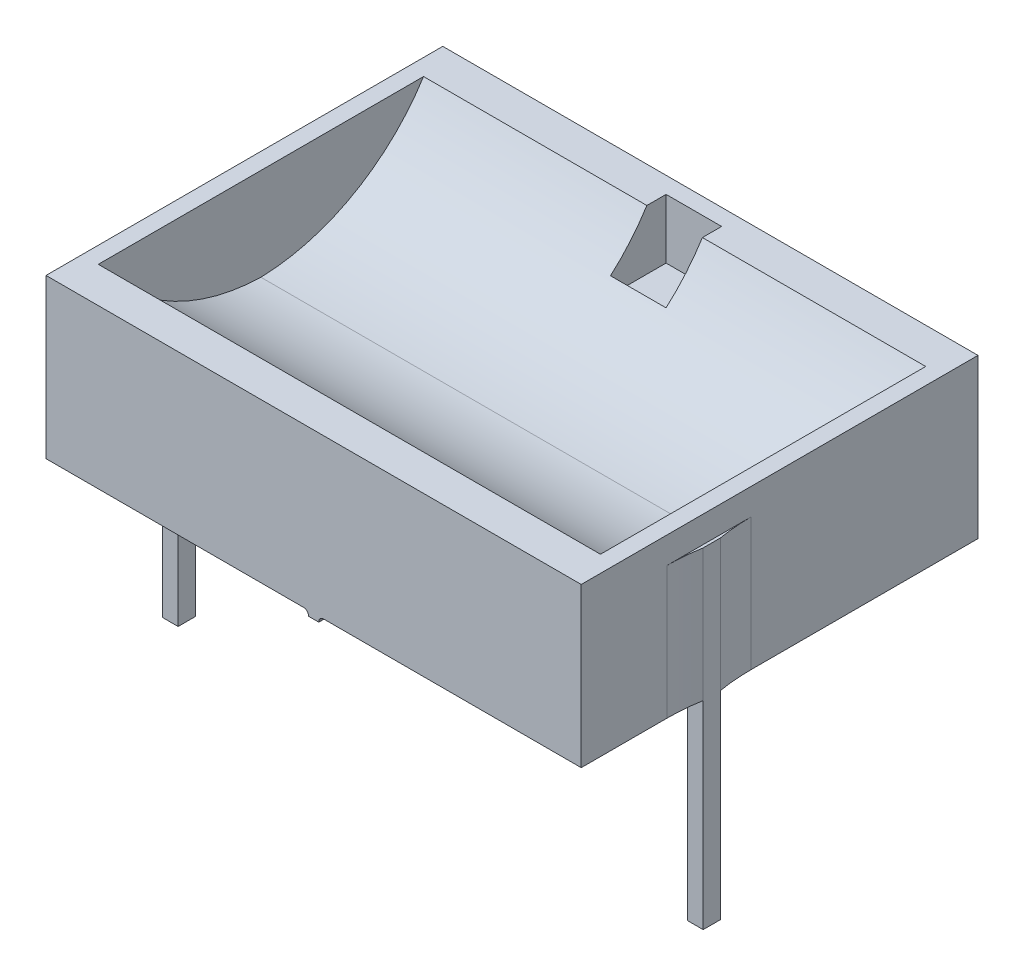
SolidWorks part; units mm, degrees
ref_plane "Front Plane" through (0, 0, 0) normal (0, 0, 1) x (1, 0, 0)
ref_plane "Top Plane" through (0, 0, 0) normal (0, 1, 0) x (1, 0, 0)
ref_plane "Right Plane" through (0, 0, 0) normal (1, 0, 0) x (0, 0, -1)
sketch "Sketch1" plane through (0, 0, 0) normal (0, 1, 0) x (1, 0, 0)
  line L1 (0, 0) -> (102.7938, 0)
  line L2 (0, 0) -> (0, 76.2)
  line L3 (0, 76.2) -> (102.7938, 76.2)
  line L4 (102.7938, 0) -> (102.7938, 76.2)
  dimension "D1" = 102.7938
  dimension "D2" = 76.2
extrude "Boss-Extrude1" add sketch "Sketch1" along normal blind 38.1
sketch "Sketch6" plane through (0, 0, 0) normal (0, -1, 0) x (1, 0, 0)
  line L0 (0, -2.5019) -> (2.5019, -2.5019) construction
  line L1 (2.5019, -2.5019) -> (100.2919, -2.5019)
  line L2 (2.5019, -2.5019) -> (2.5019, -73.6981)
  line L3 (2.5019, -73.6981) -> (100.2919, -73.6981)
  line L4 (100.2919, -2.5019) -> (100.2919, -73.6981)
  line L5 (0, -76.2) -> (0, 0) construction
  line L6 (2.5019, -2.5019) -> (2.5019, 0) construction
  line L7 (0, 0) -> (102.7938, 0) construction
  line L8 (100.2919, -76.2) -> (100.2919, -73.6981) construction
  line L9 (102.7938, -76.2) -> (0, -76.2) construction
  line L10 (102.7938, -73.6981) -> (100.2919, -73.6981) construction
  line L11 (102.7938, 0) -> (102.7938, -76.2) construction
  dimension "D1" = 97.79
sketch "Sketch2" plane through (0, 38.1, 0) normal (0, 1, 0) x (1, 0, 0)
  line L0 (3.175, 3.175) -> (0, 3.175) construction
  line L1 (3.175, 3.175) -> (99.6188, 3.175)
  line L2 (3.175, 3.175) -> (3.175, 73.025)
  line L3 (3.175, 73.025) -> (99.6188, 73.025)
  line L4 (99.6188, 3.175) -> (99.6188, 73.025)
  line L5 (0, 76.2) -> (0, 0) construction
  line L6 (3.175, 3.175) -> (3.175, 0) construction
  line L7 (0, 0) -> (102.7938, 0) construction
  line L8 (99.6188, 3.175) -> (99.6188, 0) construction
  line L9 (99.6188, 3.175) -> (102.7938, 3.175) construction
  line L10 (102.7938, 0) -> (102.7938, 76.2) construction
  line L11 (3.175, 73.025) -> (0, 73.025) construction
  line L12 (3.175, 73.025) -> (3.175, 76.2) construction
  line L13 (102.7938, 76.2) -> (0, 76.2) construction
  line L14 (99.6188, 73.025) -> (102.7938, 73.025) construction
  line L15 (99.6188, 73.025) -> (99.6188, 76.2) construction
  dimension "D1" = 3.175
extrude "Cut-Extrude1" cut sketch "Sketch2" against normal blind 25.4
sketch "Sketch3" plane through (0, 0, 0) normal (0, -1, 0) x (1, 0, 0)
  line L0 (2.5019, -2.5019) -> (2.5019, -73.6981) construction
  line L43 (100.2919, -2.5019) -> (100.2919, -73.6981) construction
  line L55 (2.5019, -22.873) -> (-0.5461, -22.873)
  line L56 (2.5019, -22.873) -> (2.5019, -26.175)
  line L57 (2.5019, -26.175) -> (-0.5461, -26.175)
  line L58 (-0.5461, -22.873) -> (-0.5461, -26.175)
  line L60 (100.2919, -22.873) -> (103.3399, -22.873)
  line L61 (100.2919, -22.873) -> (100.2919, -26.175)
  line L62 (100.2919, -26.175) -> (103.3399, -26.175)
  line L63 (103.3399, -22.873) -> (103.3399, -26.175)
  point P0 (103.3399, -24.524)
  dimension "D1" = 24.524
  dimension "D3" = 3.302
  dimension "D4" = 3.048
extrude "Boss-Extrude2" add sketch "Sketch3" along normal mid plane 50.8
sketch "Sketch7" plane through (0, 38.1, 0) normal (0, 1, 0) x (1, 0, 0)
  line L1 (0, 76.2) -> (102.7938, 76.2)
  line L2 (0, 76.2) -> (0, 0)
  line L3 (0, 0) -> (102.7938, 0)
  line L4 (102.7938, 76.2) -> (102.7938, 0)
fillet "Fillet1" radius 38.1 2 edges at (51.3969, 12.7, -3.175) (51.3969, 12.7, -73.025)
sketch "Sketch8" plane through (0, 38.1, 0) normal (0, 1, 0) x (1, 0, 0)
  line L5 (99.6188, 73.025) -> (3.175, 73.025) construction
  line L6 (56.7309, 73.025) -> (46.0629, 73.025)
  line L7 (56.7309, 73.025) -> (56.7309, 62.357)
  line L8 (56.7309, 62.357) -> (46.0629, 62.357)
  line L9 (46.0629, 73.025) -> (46.0629, 62.357)
  line L10 (51.3969, 73.025) -> (99.6188, 73.025) construction
  point P9 (51.3969, 73.025)
  dimension "D1" = 10.668
extrude "Cut-Extrude3" cut sketch "Sketch8" against normal blind 19.05
extrude "Cut-Extrude4" cut sketch "Sketch7" against normal blind 7.62
fillet "Fillet2" radius 38.1 4 edges at (0, 12.7, -22.873) (0, 12.7, -26.175) (102.7938, 12.7, -26.175) (102.7938, 12.7, -22.873)
sketch "Sketch9" plane through (0, -25.4, 0) normal (0, -1, 0) x (1, 0, 0)
  line L1 (-0.5461, -22.873) -> (2.5019, -22.873)
  line L2 (-0.5461, -22.873) -> (-0.5461, -26.175)
  line L3 (-0.5461, -26.175) -> (2.5019, -26.175)
  line L4 (2.5019, -22.873) -> (2.5019, -26.175)
  line L5 (103.3399, -22.873) -> (100.2919, -22.873)
  line L6 (103.3399, -22.873) -> (103.3399, -26.175)
  line L7 (103.3399, -26.175) -> (100.2919, -26.175)
  line L8 (100.2919, -22.873) -> (100.2919, -26.175)
extrude "Boss-Extrude3" add sketch "Sketch9" along normal blind 12.7
sketch "Sketch10" plane through (0, 0, 0) normal (0, -1, 0) x (1, 0, 0)
  line L0 (51.3969, 0) -> (0, 0) construction
  line L1 (0, 0) -> (102.7938, 0) construction
  line L2 (102.7938, -76.2) -> (0, -76.2) construction
  line L3 (50.3969, 0) -> (52.3969, 0)
  line L4 (50.3969, 0) -> (50.3969, -76.2)
  line L5 (50.3969, -76.2) -> (52.3969, -76.2)
  line L6 (52.3969, 0) -> (52.3969, -76.2)
  point P9 (51.3969, 0)
  dimension "D1" = 2
extrude "Boss-Extrude4" add sketch "Sketch10" along normal blind 1
fillet "Fillet3" radius 0.9 2 edges at (50.3969, 0, -38.1) (52.3969, 0, -38.1)
equation "\"ped_width\"= 3.85in"
equation "\"D1@Sketch6\"=\"ped_width\""
